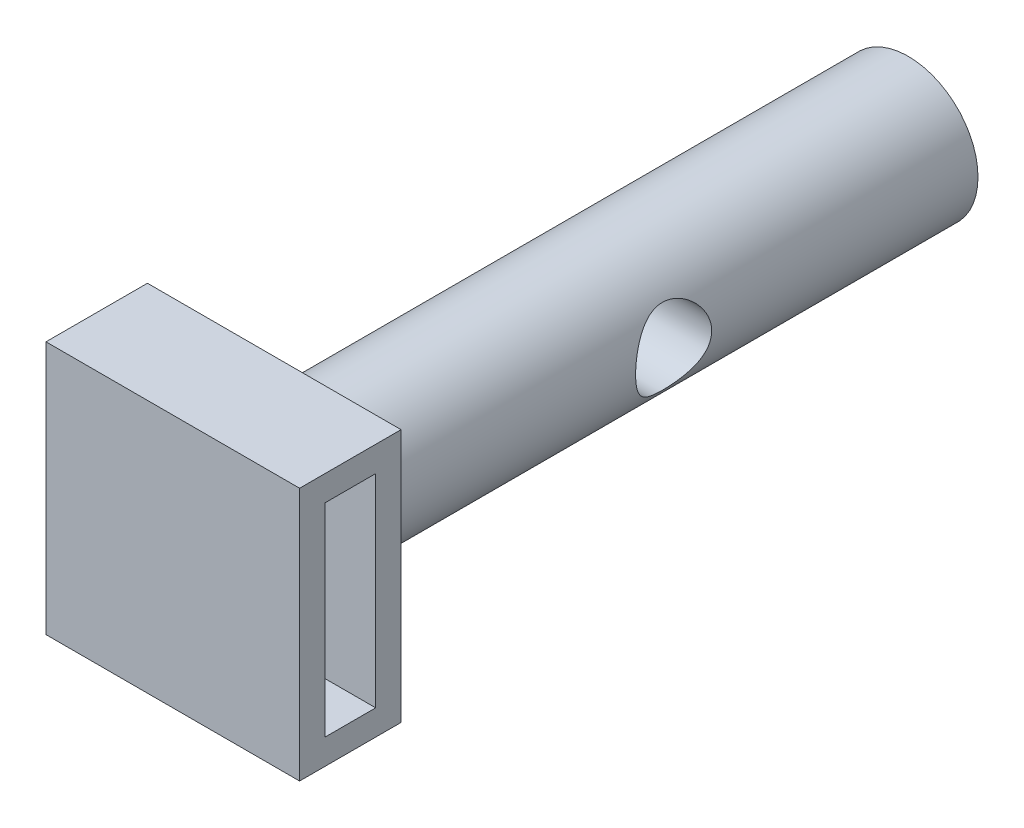
SolidWorks part; units mm, degrees
ref_plane "Front Plane" through (0, 0, 0) normal (0, 0, 1) x (1, 0, 0)
ref_plane "Top Plane" through (0, 0, 0) normal (0, 1, 0) x (1, 0, 0)
ref_plane "Right Plane" through (0, 0, 0) normal (1, 0, 0) x (0, 0, -1)
sketch "Sketch2" plane through (0, 0, 0) normal (0, 0, 1) x (1, 0, 0)
  circle A4 centre (0, 0) radius 2.75
  point P3 (25, 0)
  dimension "D1" = 5.5
ref_plane "Plane1" through (0, 0, 25) normal (0, 0, 1) x (1, 0, 0)
sketch "Sketch3" plane through (0, 0, 25) normal (0, 0, 1) x (1, 0, 0)
  line L0 (-5, 5) -> (5, 5)
  line L1 (-5, 5) -> (-5, -5)
  line L2 (-5, -5) -> (5, -5)
  line L3 (5, 5) -> (5, -5)
  circle A0 centre (0, 0) radius 2.75
  point P3 (0, 5)
  point P9 (5, 0)
  dimension "D1" = 5.5
  dimension "D2" = 10
loft "Loft1" add profiles "Sketch2", "Sketch3" connector at (0.2399, 2.7395, 0) connector at (0.0916, 2.7485, 25)
extrude "Boss-Extrude4" add sketch "Sketch3<7>" along normal blind 4 contours A0 L3 L0 L1 | A0 L1 L2 L3 | A0 | A0 L0 L1 | A0 L2 L3 region at (0, 4.8586, 25) region at (0, 0, 25)
sketch "Sketch3<7>" plane through (0, 0, 25) normal (0, 0, 1) x (1, 0, 0) same geometry as "Sketch3"
sketch "Sketch8" plane through (5, 0, 0) normal (1, 0, 0) x (0, 0, -1)
  line L0 (-29, 5) -> (-29, -5) construction
  line L1 (-28, 4) -> (-26, 4)
  line L2 (-28, 4) -> (-28, -4)
  line L3 (-28, -4) -> (-26, -4)
  line L4 (-26, 4) -> (-26, -4)
  line L5 (-29, 5) -> (-25, 5) construction
  point P4 (-28, 0)
  point P7 (-29, 0)
  point P8 (-27, 4)
  point P11 (-27, 5)
  dimension "D1" = 2
  dimension "D2" = 8
extrude "Cut-Extrude2" cut sketch "Sketch8" against normal through all both and the other way through all
fillet "Fillet1" radius 1 1 edges at (2.75, 0, 25)
ref_plane "Plane2" [suppressed] through (-3.4151, 5.9151, 0) normal (0.5, -0.866, 0) x (0, 0, -1)
ref_plane "Plane3" [suppressed] through (2.9244, -5.0652, 0) normal (0.5, -0.866, 0) x (0, 0, -1)
sketch "Sketch10" [suppressed] plane through (2.9244, -5.0652, 0) normal (0.5, -0.866, 0) x (0, 0, -1)
  line L1 (-15.5, -3.25) -> (0, -3.25) construction
  circle A0 centre (-16.5644, -7) radius 1.25
  dimension "D1" = 7
  dimension "D3" = 2.5
  dimension "D2" = 3.75
extrude "Cut-Extrude3" [suppressed] cut sketch "Sketch10" against normal blind 3 from surface contours A0 starting at face at (2.75, 0, 24)
mirror "Mirror1" [suppressed] about plane through (0, 0, 0) normal (1, 0, 0)
sketch "Sketch11" plane through (0, 0, 0) normal (1, 0, 0) x (0, 0, -1)
  line L1 (0, 0) -> (-24, 0) construction
  line L2 (0, -2.75) -> (0, 2.75) construction
  line L3 (-24, -2.75) -> (-24, 2.75) construction
  circle A0 centre (-12, 0) radius 1.5
  point P2 (0, 0)
extrude "Cut-Extrude4" cut sketch "Sketch11" against normal through all both and the other way through all
